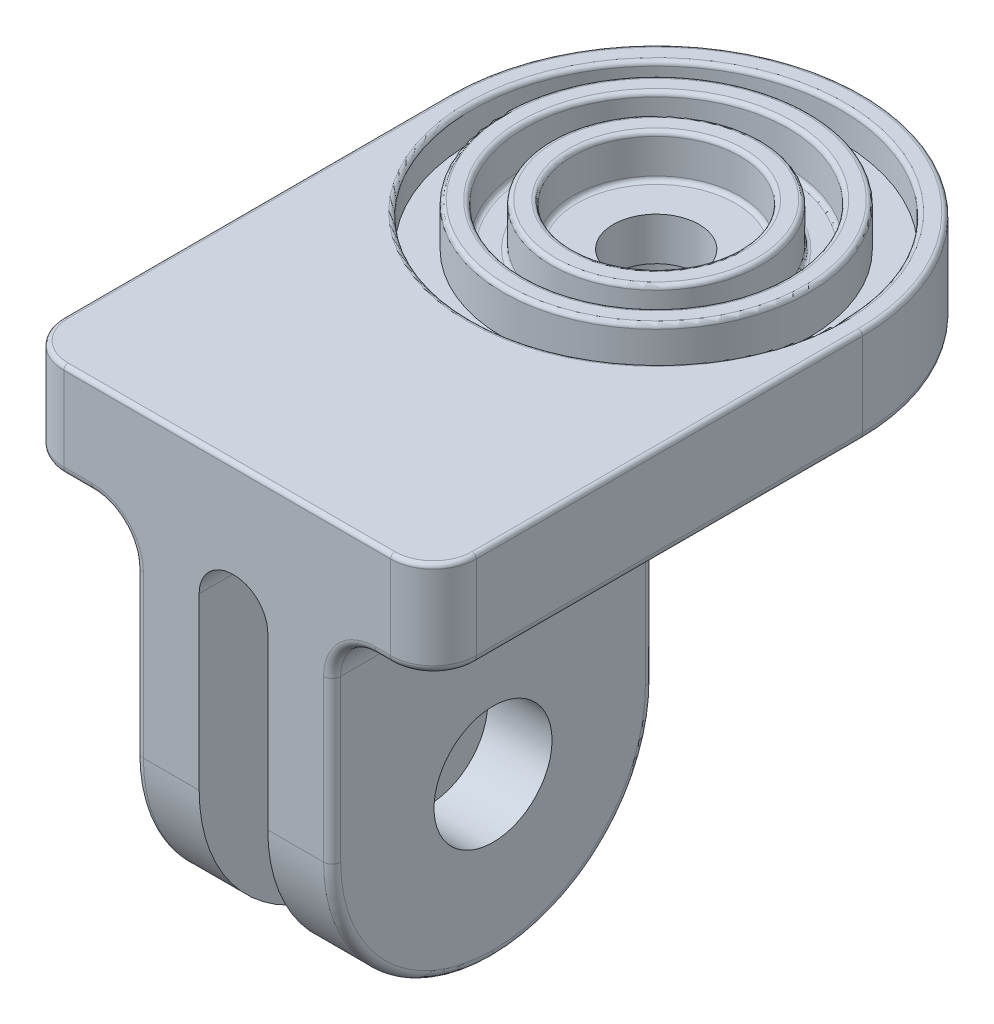
SolidWorks part; units mm, degrees
ref_plane "Ebene vorne" through (0, 0, 0) normal (0, 0, 1) x (1, 0, 0)
ref_plane "Ebene oben" through (0, 0, 0) normal (0, 1, 0) x (1, 0, 0)
ref_plane "Ebene rechts" through (0, 0, 0) normal (1, 0, 0) x (0, 0, -1)
sketch "Skizze1" plane through (0, 0, 0) normal (0, 1, 0) x (1, 0, 0)
  circle A0 centre (0, 0) radius 3.9
  circle A1 centre (0, 0) radius 4.9
  circle A2 centre (0, 0) radius 7.125
  circle A3 centre (0, 0) radius 6.15
  dimension "D1" = 7.8
  dimension "D2" = 9.8
  dimension "D3" = 14.25
  dimension "D4" = 12.3
extrude "Aufsatz-Linear austragen1" add sketch "Skizze1" along normal blind 2 contours A1 A0 | A2 A3
sketch "Skizze2" plane through (0, 0, 0) normal (0, 1, 0) x (1, 0, 0)
  circle A0 centre (0, 0) radius 8.6168
  circle A1 centre (0, 0) radius 9.6168
  dimension "D1" = 17.2337
  dimension "D2" = 1
extrude "Aufsatz-Linear austragen2" add sketch "Skizze2" along normal blind 1.5 separate body
sketch "Skizze3" plane through (0, 0, 0) normal (0, -1, 0) x (1, 0, 0)
  circle A0 centre (0, 0) radius 9.6168 construction
  circle A1 centre (0, 0) radius 9.6168
  circle A2 centre (0, 0) radius 2
  dimension "D1" = 4
extrude "Aufsatz-Linear austragen3" add sketch "Skizze3" along normal blind 2
fillet "Verrundung1" radius 0.2 1 edges at (0, 0, 3.9)
fillet "Verrundung2" radius 0.2 2 edges at (0, 0, 6.15) (0, 0, 4.9)
fillet "Verrundung3" radius 0.2 5 edges at (0, 2, 4.9) (0, 2, 3.9) (0, 2, 6.15) (0, 2, 7.125) (0, 1.5, 8.6168)
sketch "Skizze4" plane through (0, 0, 0) normal (0, 1, 0) x (1, 0, 0)
  line L0 (-9.6168, 0) -> (-9.6168, -20)
  line L1 (-9.6168, -20) -> (9.6168, -20)
  line L2 (9.6168, -20) -> (9.6168, 0)
  arc A1 (9.6168, 0) -> (-9.6168, 0) centre (0, 0) ccw
  circle A2 centre (0, 0) radius 3
  dimension "D1" = 6
  dimension "D2" = 20
extrude "Aufsatz-Linear austragen4" add sketch "Skizze4" against normal blind 3
sketch "Skizze5" plane through (0, -3, 0) normal (0, -1, 0) x (1, 0, 0)
  line L0 (-9.6168, 20) -> (9.6168, 20) construction
  line L1 (-4.3058, 20) -> (-1.3058, 20)
  line L2 (-4.3058, 20) -> (-4.3058, 5)
  line L3 (-4.3058, 5) -> (-1.3058, 5)
  line L4 (4.8942, 20) -> (4.8942, 5)
  line L5 (0.2942, 0) -> (0.2942, 20) construction
  line L6 (-1.3058, 20) -> (-1.3058, 5)
  line L7 (1.8942, 20) -> (1.8942, 5)
  line L8 (1.8942, 20) -> (4.8942, 20)
  line L9 (1.8942, 5) -> (4.8942, 5)
  dimension "D1" = 9.2
  dimension "D2" = 4.6
  dimension "D3" = 15
  dimension "D4" = 3.2
  dimension "D5" = 1.6
extrude "Aufsatz-Linear austragen5" add sketch "Skizze5" along normal blind 17
fillet "Verrundung4" radius 7.5 4 edges at (3.3942, -20, 20) (-2.8058, -20, 20) (3.3942, -20, 5) (-2.8058, -20, 5)
sketch "Skizze6" plane through (4.8942, 0, 0) normal (1, 0, 0) x (0, 0, -1)
  line L0 (-20, -12.5) -> (-5, -12.5) construction
  line L1 (-12.5, -20) -> (-12.5, -12.5) construction
  circle A0 centre (-12.5, -12.5) radius 2.75
  dimension "D1" = 5.5
extrude "Schnitt-Linear austragen1" cut sketch "Skizze6" against normal through all
fillet "Verrundung5" radius 2 4 edges at (3.3942, -3, 5) (-2.8058, -3, 5) (-4.3058, -3, 12.5) (4.8942, -3, 12.5)
fillet "Verrundung6" radius 1.56 2 edges at (-1.3058, -3, 11.5) (1.8942, -3, 11.5)
fillet "Verrundung7" radius 0.4 17 edges at (-9.6168, -3, 10) (0, -3, -9.6168) (5.48, -3.5858, 4.4142) (4.8942, -8.75, 5) (4.8942, -17.8033, 7.1967) (4.8942, -17.8033, 17.8033) (8.2555, -3, 20) (5.48, -3.5858, 20) (-4.8916, -3.5858, 4.4142) (-4.3058, -8.75, 5) (-7.9613, -3, 20) (-4.8916, -3.5858, 20) (-4.3058, -8.75, 20) (-4.3058, -17.8033, 17.8033) (9.6168, -3, 10) (4.8942, -8.75, 20) (-4.3058, -17.8033, 7.1967)
fillet "Verrundung9" radius 2 4 edges at (-9.4997, -2.8828, 19.8828) (9.4997, -2.8828, 19.8828) (9.6168, -1.3, 20) (-9.6168, -1.3, 20)
sketch "Skizze7" plane through (0, 0, 0) normal (0, 1, 0) x (1, 0, 0)
  line L3 (-7.6168, -20) -> (7.6168, -20)
  line L4 (9.6168, -18) -> (9.6168, 0)
  line L5 (-9.6168, 0) -> (-9.6168, -18)
  line L6 (-7.6168, -20) -> (7.6168, -20)
  line L7 (9.6168, -18) -> (9.6168, 0)
  line L8 (-9.6168, 0) -> (-9.6168, -18)
  arc A3 (7.6168, -20) -> (9.6168, -18) centre (7.6168, -18) ccw
  arc A4 (-9.6168, 0) -> (9.6168, 0) centre (0, 0) ccw
  arc A5 (-9.6168, -18) -> (-7.6168, -20) centre (-7.6168, -18) ccw
  arc A6 (7.6168, -20) -> (9.6168, -18) centre (7.6168, -18) ccw
  arc A7 (-9.6168, 0) -> (9.6168, 0) centre (0, 0) ccw
  arc A8 (-9.6168, -18) -> (-7.6168, -20) centre (-7.6168, -18) ccw
  dimension "D1" = 0
extrude "Aufsatz-Linear austragen6" add sketch "Skizze7" along normal up to surface (1.5 mm away) up to face at (0, 1.5, 8.8168)
fillet "Verrundung12" radius 0.2 6 edges at (9.031, 1.5, 19.4142) (0, 1.5, 20) (-9.031, 1.5, 19.4142) (-9.6168, 1.5, 9) (0, 1.5, -9.6168) (9.6168, 1.5, 9)
equation "\"D2@Skizze5\"=\"D1@Skizze5\"/2"
equation "\"D5@Skizze5\"=\"D4@Skizze5\"/2"
